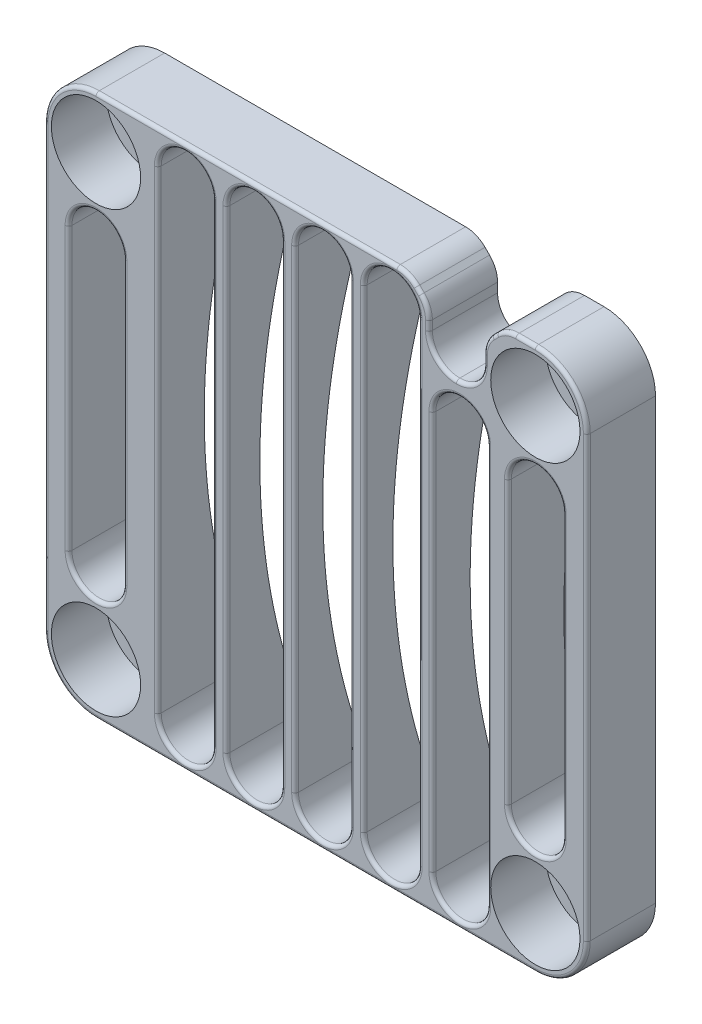
SolidWorks part; units mm, degrees
ref_plane "Front Plane" through (0, 0, 0) normal (0, 0, 1) x (1, 0, 0)
ref_plane "Top Plane" through (0, 0, 0) normal (0, 1, 0) x (1, 0, 0)
ref_plane "Right Plane" through (0, 0, 0) normal (1, 0, 0) x (0, 0, -1)
sketch "Sketch1" plane through (0, 0, 0) normal (0, 0, 1) x (1, 0, 0)
  line L0 (-16, 20) -> (16, 20) construction
  line L1 (-20, -20) -> (20, -20) construction
  line L2 (-20, -20) -> (-20, 20) construction
  line L3 (-20, 20) -> (20, 20) construction
  line L4 (20, -20) -> (20, 20) construction
  line L5 (-20, -20) -> (20, 20) construction
  line L6 (-20, 20) -> (20, -20) construction
  line L7 (20, 16) -> (20, -16) construction
  line L8 (-20, 16) -> (-20, -16) construction
  line L9 (16, -20) -> (-16, -20) construction
  line L10 (19.75, 16) -> (19.75, -16)
  line L11 (16, -19.75) -> (-16, -19.75)
  line L12 (-19.75, 16) -> (-19.75, -16)
  line L13 (-16, 19.75) -> (16, 19.75)
  arc A0 (-16, 20) -> (-20, 16) centre (-16, 16) ccw construction
  arc A1 (16, 20) -> (20, 16) centre (16, 16) cw construction
  arc A2 (-20, -16) -> (-16, -20) centre (-16, -16) ccw construction
  arc A3 (20, -16) -> (16, -20) centre (16, -16) cw construction
  arc A4 (20, 16) -> (16, 20) centre (16, 16) ccw construction
  arc A5 (16, 19.75) -> (19.75, 16) centre (16, 16) cw
  arc A6 (19.75, -16) -> (16, -19.75) centre (16, -16) cw
  arc A7 (-19.75, -16) -> (-16, -19.75) centre (-16, -16) ccw
  arc A8 (-16, 19.75) -> (-19.75, 16) centre (-16, 16) ccw
  point P0 (0, 0)
  dimension "D1" = 0.25
extrude "Boss-Extrude1" add sketch "Sketch1" along normal blind 5
sketch "Sketch2" plane through (0, 0, 0) normal (0, 0, -1) x (-1, 0, 0)
  circle A0 centre (-16, 16) radius 1.75
  circle A1 centre (16, 16) radius 1.75
  circle A2 centre (16, -16) radius 1.75
  circle A3 centre (-16, -16) radius 1.75
  circle A4 centre (-16, -16) radius 1.5 construction
  circle A5 centre (16, -16) radius 1.5 construction
  circle A6 centre (16, 16) radius 1.5 construction
  circle A7 centre (-16, 16) radius 1.5 construction
  dimension "D1" = 3.5
extrude "Cut-Extrude1" cut sketch "Sketch2" against normal through all both and the other way through all
sketch "Sketch3" plane through (0, 0, 5) normal (0, 0, 1) x (1, 0, 0)
  circle A0 centre (-16, 16) radius 3.25
  circle A1 centre (-16, 16) radius 1.75 construction
  dimension "D1" = 6.5
extrude "Cut-Extrude2" cut sketch "Sketch3" against normal blind 4
mirror "Mirror1" about plane through (0, 0, 0) normal (1, 0, 0) of "Cut-Extrude2"
mirror "Mirror2" about plane through (0, 0, 0) normal (0, 1, 0) of "Mirror1"
sketch "Sketch4" plane through (0, 0, 5) normal (0, 0, 1) x (1, 0, 0)
  line L0 (-16, 12.75) -> (-16, -12.75) construction
  line L1 (-16, 10.25) -> (-16, -10.25) construction
  line L2 (-14, 10.25) -> (-14, -10.25)
  line L3 (-18, 10.25) -> (-18, -10.25)
  circle A0 centre (-16, 16) radius 3.25 construction
  circle A1 centre (-16, 16) radius 3.25 construction
  circle A2 centre (-16, -16) radius 3.25 construction
  arc A3 (-14, 10.25) -> (-18, 10.25) centre (-16, 10.25) ccw
  arc A4 (-18, -10.25) -> (-14, -10.25) centre (-16, -10.25) ccw
  point P11 (-16, 0)
  dimension "D1" = 2.5
  dimension "D2" = 4
extrude "Cut-Extrude3" cut sketch "Sketch4" against normal through all both and the other way through all
mirror "Mirror3" about plane through (0, 0, 0) normal (1, 0, 0) of "Cut-Extrude3"
sketch "Sketch5" plane through (0, 0, 5) normal (0, 0, 1) x (1, 0, 0)
  line L0 (-19.75, 0) -> (-18, 0) construction
  line L1 (-19.75, 16) -> (-19.75, -16) construction
  line L2 (-18, 10.25) -> (-18, -10.25) construction
  line L3 (-11.5, 0) -> (-14, 0) construction
  line L4 (-14, 10.25) -> (-14, -10.25) construction
  line L5 (-9.5, 17.25) -> (-9.5, -17.25) construction
  line L6 (-7.5, 17.25) -> (-7.5, -17.25)
  line L7 (-11.5, 17.25) -> (-11.5, -17.25)
  line L8 (-16, 12.25) -> (-16, 12.75) construction
  line L9 (-9.5, 19.75) -> (-9.5, 19.25) construction
  line L10 (16, 19.75) -> (-16, 19.75) construction
  arc A0 (-7.5, 17.25) -> (-11.5, 17.25) centre (-9.5, 17.25) ccw
  arc A1 (-11.5, -17.25) -> (-7.5, -17.25) centre (-9.5, -17.25) ccw
  arc A2 (-14, 10.25) -> (-18, 10.25) centre (-16, 10.25) ccw construction
  point P8 (-18.875, 0)
  point P10 (-9.5, 0)
  dimension "D1" = 2.5
extrude "Cut-Extrude4" cut sketch "Sketch5" against normal through all both and the other way through all
pattern_linear "LPattern1" count 5 spacing 5 along (1, 0, 0) skipping (4, 0) of "Cut-Extrude4"
sketch "Sketch9" plane through (0, 0, 5) normal (0, 0, 1) x (1, 0, 0)
  line L0 (16, 19.75) -> (-16, 19.75) construction
  line L1 (12.25, 19.75) -> (8.25, 19.75)
  line L2 (12.25, 19.75) -> (12.25, 14.75) construction
  line L3 (12.25, 14.75) -> (8.25, 14.75)
  line L4 (8.25, 19.75) -> (8.25, 14.75) construction
  line L5 (12.25, 19.75) -> (8.25, 14.75) construction
  line L6 (12.25, 14.75) -> (8.25, 19.75) construction
  line L7 (19.75, -16) -> (19.75, 16) construction
  line L9 (8.25, 19.75) -> (6.75, 19.75)
  line L10 (6.75, 19.75) -> (8.25, 18.25)
  line L11 (8.25, 18.25) -> (8.25, 14.75)
  line L12 (12.25, 19.75) -> (13.75, 19.75)
  line L13 (13.75, 19.75) -> (12.25, 18.25)
  line L14 (12.25, 18.25) -> (12.25, 14.75)
  point P4 (10.25, 17.25)
  dimension "D1" = 5
  dimension "D2" = 9.5
  dimension "D3" = 4
  dimension "D4" = 45
  dimension "D5" = 1.5
extrude "Cut-Extrude5" cut sketch "Sketch9" against normal through all both and the other way through all
fillet "Fillet5" radius 2 6 edges at (13.75, 19.75, 2.5) (12.25, 18.25, 2.5) (6.75, 19.75, 2.5) (8.25, 18.25, 2.5) (8.25, 14.75, 2.5) (12.25, 14.75, 2.5)
sketch "Sketch10" plane through (0, 0, 5) normal (0, 0, 1) x (1, 0, 0)
  line L0 (10.5, 11.7657) -> (10.5, -17.25) construction
  line L1 (12.5, 11.7657) -> (12.5, -17.25)
  line L2 (8.5, 11.7657) -> (8.5, -17.25)
  line L3 (10.25, 14.75) -> (10.25, 13.75) construction
  line L5 (5.5, -19.25) -> (12.5, -19.25) construction
  line L6 (7.5, -17.25) -> (7.5, 17.25) construction
  line L7 (0.5, 17.25) -> (5.5, 17.25) construction
  line L8 (10.5, 11.7657) -> (5.5, 11.7657) construction
  line L9 (2.5, 0) -> (3.5, 0) construction
  line L10 (2.5, -17.25) -> (2.5, 17.25) construction
  line L11 (3.5, 17.25) -> (3.5, -17.25) construction
  arc A0 (12.5, 11.7657) -> (8.5, 11.7657) centre (10.5, 11.7657) ccw
  arc A1 (8.5, -17.25) -> (12.5, -17.25) centre (10.5, -17.25) ccw
  arc A3 (3.5, -17.25) -> (7.5, -17.25) centre (5.5, -17.25) ccw construction
  arc A4 (7.5, 17.25) -> (3.5, 17.25) centre (5.5, 17.25) ccw construction
  point P2 (10.5, -2.7422)
  point P10 (10.25, 14.75)
  point P18 (0, 0)
  point P25 (0, 0)
  point P34 (5.5, 17.25)
  dimension "D1" = 1
extrude "Cut-Extrude6" cut sketch "Sketch10" against normal through all both and the other way through all
ref_axis "Axis1" through (0, 0, -0.25) along (0, 0, 1)
sketch "Sketch7" plane through (0, 0, 0) normal (0, 0, 1) x (1, 0, 0)
  line L0 (0, -19.75) -> (0, -16.75) construction
  line L1 (-16, -19.75) -> (16, -19.75) construction
  circle A0 centre (0, 0) radius 16.75
  dimension "D1" = 3
sketch "Sketch6" plane through (0, 0, 0) normal (0, 1, 0) x (1, 0, 0)
  line L0 (0, 0) -> (0, -3)
  line L1 (16, 0) -> (14.5784, 0) construction
  line L2 (0, 0) -> (16.75, 0)
  line L3 (0, -3) -> (16.75, -3) construction
  line L4 (16.75, -3) -> (16.75, 0) construction
  line L7 (0, 0.25) -> (0, -5.25) construction
  arc A1 (0, -3) -> (16.75, 0) centre (0, 45.2604) ccw
  dimension "D1" = 3
revolve "Cut-Revolve1" cut sketch "Sketch6" angle 360 about axis through (0, 0, -0.25) along (0, 0, 1)
fillet "Fillet3" radius 0.25 28 edges at (16, -12.25, 5) (18, 0, 5) (16, 12.25, 5) (5.5, 19.25, 5) (7.5, 0, 5) (5.5, -19.25, 5) (0.5, 19.25, 5) (2.5, 0, 5) (0.5, -19.25, 5) (-9.5, 19.25, 5) (-7.5, 0, 5) (-9.5, -19.25, 5) (-4.5, 19.25, 5) (-2.5, 0, 5) (-4.5, -19.25, 5) (-16, 12.25, 5) (-14, 0, 5) (-16, -12.25, 5) (14, 0, 5) (3.5, 0, 5) (-1.5, 0, 5) (-11.5, 0, 5) (-6.5, 0, 5) (-18, 0, 5) (12.5, -2.7422, 5) (10.5, -19.25, 5) (8.5, -2.7422, 5) (10.5, 13.7657, 5)
fillet "Fillet2" radius 0.25 19 edges at (15.2892, 19.75, 5) (-5.0392, 19.75, 5) (18.6517, 18.6517, 5) (19.75, 0, 5) (18.6517, -18.6517, 5) (0, -19.75, 5) (-18.6517, -18.6517, 5) (-19.75, 0, 5) (-18.6517, 18.6517, 5) (8.25, 17.0858, 5) (8.0978, 18.1869, 5) (7.5, 19, 5) (6.6869, 19.5978, 5) (12.25, 17.0858, 5) (12.4022, 18.1869, 5) (13, 19, 5) (13.8131, 19.5978, 5) (8.8358, 15.3358, 5) (11.6642, 15.3358, 5)
